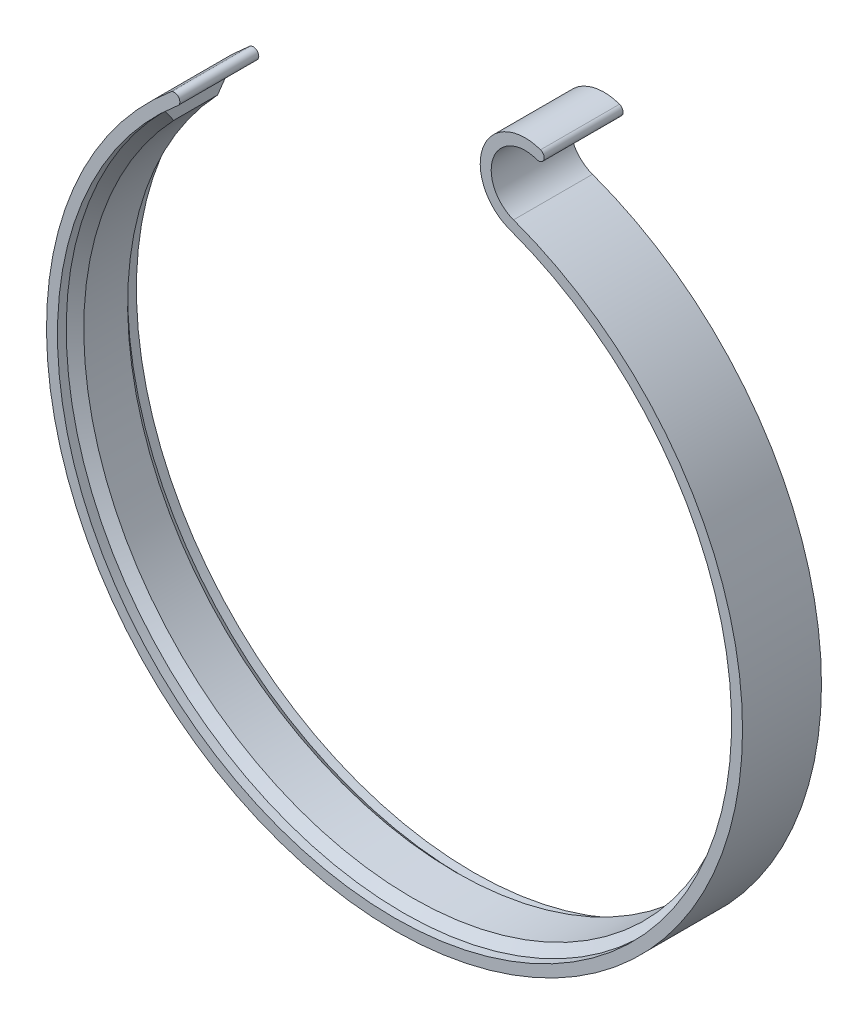
SolidWorks part; units mm, degrees
ref_plane "Front Plane" through (0, 0, 0) normal (0, 0, 1) x (1, 0, 0)
ref_plane "Top Plane" through (0, 0, 0) normal (0, 1, 0) x (1, 0, 0)
ref_plane "Right Plane" through (0, 0, 0) normal (1, 0, 0) x (0, 0, -1)
sketch "Sketch1" plane through (0, 0, 0) normal (0, 0, 1) x (1, 0, 0)
  line L0 (0, 0) -> (0, 98.4093) construction
  line L4 (29.79, 81.8472) -> (0, 0) construction
  line L5 (0, 0) -> (-59.8253, 71.2971) construction
  arc A0 (-49.3982, 58.8705) -> (26.2842, 72.2154) centre (0, 0) ccw
  arc A1 (-51.0052, 60.7856) -> (27.1393, 74.5646) centre (0, 0) ccw
  arc A4 (26.2842, 72.2154) -> (33.2957, 91.4791) centre (29.79, 81.8472) cw
  arc A5 (27.1393, 74.5646) -> (32.4406, 89.1298) centre (29.79, 81.8472) cw
  arc A6 (33.2957, 91.4791) -> (32.5369, 89.0992) centre (32.8681, 90.3045) cw
  arc A7 (32.4406, 89.1298) -> (33.2957, 91.4791) centre (32.8681, 90.3045) ccw
  arc A10 (-49.3982, 58.8705) -> (-49.0561, 60.3282) centre (-50.2017, 59.8281) ccw
  arc A11 (-49.0561, 60.3282) -> (-51.0052, 60.7856) centre (-50.2017, 59.8281) ccw
  point P10 (0, 0)
  point P13 (0, 0)
  point P16 (-24.8389, 73.8228)
  point P17 (-25.5436, 73.4406)
  point P18 (0, 0)
  point P22 (29.4637, 80.9508)
  point P23 (0, 0)
  point P24 (0, 0)
  point P25 (0, 0)
  point P26 (32.9591, 90.5545)
  dimension "D1" = 2.5
  dimension "D2" = 153.7
  dimension "D3" = 9
  dimension "D4" = 40
  dimension "D6" = 2.5
  dimension "D5" = 20
extrude "Boss-Extrude1" add sketch "Sketch1" along normal blind 18 contours A10 A11 A1 A5 A7 A6 A4 A0 region at (13.7505, -77.9832, 0)
sketch "Sketch2" plane through (0, 0, 0) normal (1, 0, 0) x (0, 0, -1)
  line L1 (-15, -73.8981) -> (-15, -69.3473) construction
  line L7 (-14, -74.85) -> (-16, -76.85)
  line L8 (-16, -76.85) -> (-2, -76.85)
  line L9 (-14, -74.85) -> (-4, -74.85)
  line L10 (-18, -69.3473) -> (0, -69.3473) construction
  line L12 (-9, -69.3473) -> (-9, -89.1861) construction
  line L13 (-4, -74.85) -> (-2, -76.85)
  line L14 (0, 0) -> (-38.791, 0) construction
  line L15 (-18, 74.5646) -> (-18, -79.35) construction
  line L16 (0, -79.35) -> (0, 74.5646) construction
  point P5 (-18, -69.3473)
  point P6 (0, -69.5049)
  point P17 (-9, -74.85)
  point P18 (-9, -76.85)
  point P21 (0, 0)
  point P22 (0, 0)
  point P23 (-15, -67.2275)
  point P24 (-15, -73.8981)
  point P25 (-15, -68.8725)
  point P27 (0, 0)
  dimension "D1" = 45
  dimension "D2" = 3
  dimension "D3" = 2
  dimension "D4" = 1
  dimension "D5" = 76.85
revolve "Revolve1" add sketch "Sketch2" angle 155 about L14 other way angle 135
chamfer "Chamfer1" distance 2 angle 45 2 edges at (31.633, 67.8371, 9) (-52.9269, 52.9269, 9)
